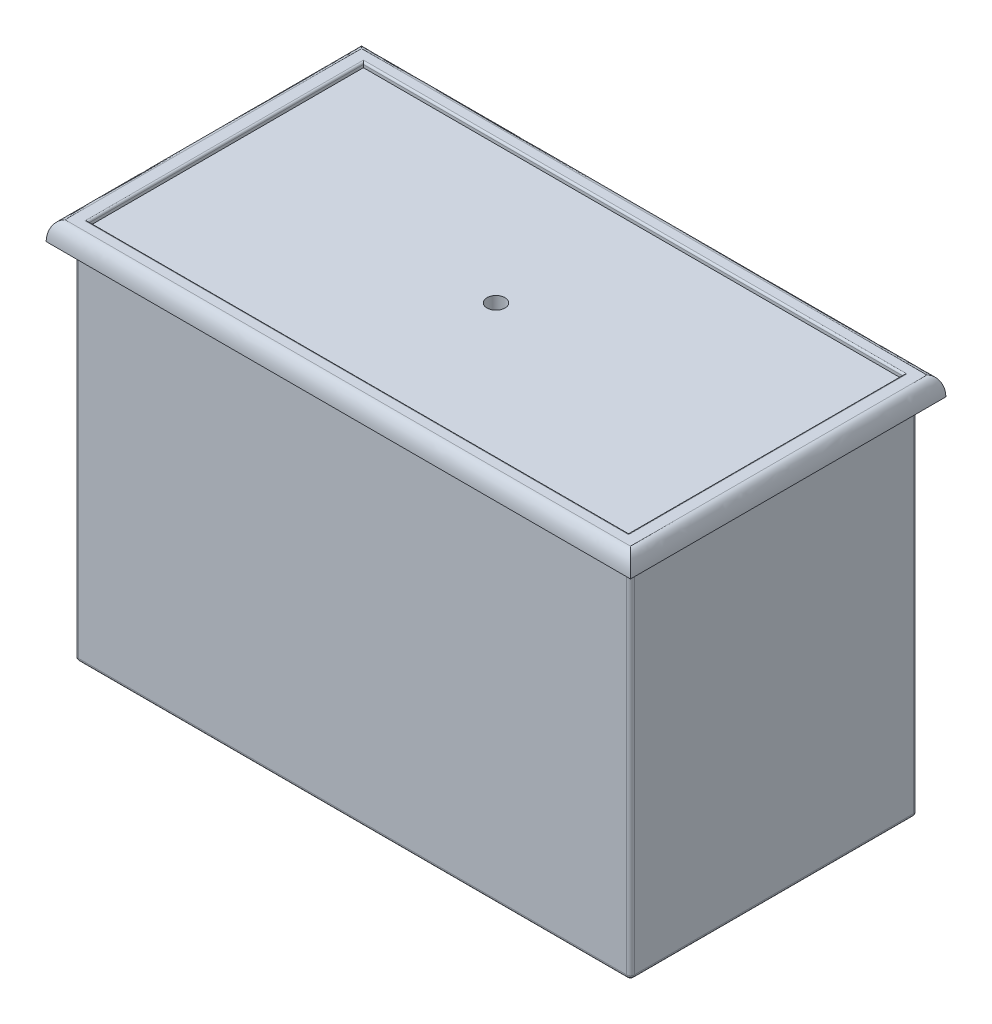
SolidWorks part; units mm, degrees
ref_plane "Front Plane" through (0, 0, 0) normal (0, 0, 1) x (1, 0, 0)
ref_plane "Top Plane" through (0, 0, 0) normal (0, 1, 0) x (1, 0, 0)
ref_plane "Right Plane" through (0, 0, 0) normal (1, 0, 0) x (0, 0, -1)
sketch "Sketch2" plane through (0, 0, 0) normal (0, 1, 0) x (1, 0, 0)
  line L0 (-290.5, 148.5) -> (290.5, 148.5)
  line L1 (-293.5, 151.5) -> (293.5, 151.5)
  line L2 (-293.5, 151.5) -> (-293.5, -151.5)
  line L3 (-293.5, -151.5) -> (293.5, -151.5)
  line L4 (293.5, 151.5) -> (293.5, -151.5)
  line L5 (-293.5, 151.5) -> (293.5, -151.5) construction
  line L6 (-293.5, -151.5) -> (293.5, 151.5) construction
  line L7 (290.5, 148.5) -> (290.5, -148.5)
  line L8 (-290.5, -148.5) -> (290.5, -148.5)
  line L9 (-290.5, 148.5) -> (-290.5, -148.5)
  point P0 (0, 0)
  dimension "D1" = 303
  dimension "D2" = 587
  dimension "D3" = 3
extrude "Walls" add sketch "Sketch2" along normal blind 380 contours L0 L7 L8 L9 | L2 L1 L4 L3
sketch "Sketch3" plane through (0, 0, 0) normal (0, -1, 0) x (1, 0, 0)
  line L1 (293.5, 151.5) -> (-293.5, 151.5)
  line L2 (293.5, 151.5) -> (293.5, -151.5)
  line L3 (293.5, -151.5) -> (-293.5, -151.5)
  line L4 (-293.5, 151.5) -> (-293.5, -151.5)
  line L5 (293.5, 151.5) -> (-293.5, -151.5) construction
  line L6 (293.5, -151.5) -> (-293.5, 151.5) construction
  point P0 (0, 0)
extrude "Base" add sketch "Sketch3" along normal blind 3
sketch "Sketch5" plane through (0, 380, 0) normal (0, 1, 0) x (1, 0, 0)
  line L8 (-308.5, -166.5) -> (308.5, -166.5)
  line L9 (-308.5, 166.5) -> (-308.5, -166.5)
  line L10 (308.5, -166.5) -> (308.5, 166.5)
  line L11 (308.5, 166.5) -> (-308.5, 166.5)
  line L12 (-308.5, -166.5) -> (308.5, -166.5)
  line L13 (-308.5, 166.5) -> (-308.5, -166.5)
  line L14 (308.5, -166.5) -> (308.5, 166.5)
  line L15 (308.5, 166.5) -> (-308.5, 166.5)
  dimension "D1" = 15
extrude "Lid" add sketch "Sketch5" along normal blind 20
sketch "Sketch7" plane through (0, 400, 0) normal (0, 1, 0) x (1, 0, 0)
  line L1 (-285, 145) -> (285, 145)
  line L2 (-285, 145) -> (-285, -145)
  line L3 (-285, -145) -> (285, -145)
  line L4 (285, 145) -> (285, -145)
  line L5 (-285, 145) -> (285, -145) construction
  line L6 (-285, -145) -> (285, 145) construction
  point P0 (0, 0)
  dimension "D1" = 570
  dimension "D2" = 290
extrude "Lid Divet" cut sketch "Sketch7" against normal blind 5
fillet "Fillet1" radius 20 4 edges at (0, 400, -166.5) (308.5, 400, 0) (0, 400, 166.5) (-308.5, 400, 0) second distance 10 first distance on face at (0, 390, -166.5) first distance on face at (308.5, 390, 0) first distance on face at (0, 390, 166.5) first distance on face at (-308.5, 390, 0)
fillet "Fillet2" radius 2 4 edges at (285, 400, 0) (0, 400, 145) (-285, 400, 0) (0, 400, -145)
fillet "Fillet3" radius 4 8 edges at (0, -3, 151.5) (293.5, -3, 0) (0, -3, -151.5) (-293.5, -3, 0) (293.5, 188.5, -151.5) (293.5, 188.5, 151.5) (-293.5, 188.5, -151.5) (-293.5, 188.5, 151.5)
sketch "Sketch8" plane through (0, 395, 0) normal (0, 1, 0) x (1, 0, 0)
  circle A0 centre (0, 0) radius 9.525
  dimension "D1" = 19.05
extrude "Inlet" cut sketch "Sketch8" against normal up to next
sketch "Sketch9" plane through (0, -3, 0) normal (0, -1, 0) x (1, 0, 0)
  line L0 (-289.5, 147.5) -> (-289.5, -147.5) construction
  circle A0 centre (-259.5, 0) radius 9.525
  dimension "D1" = 19.05
  dimension "D2" = 30
extrude "Cut-Extrude3" cut sketch "Sketch9" against normal up to next
equation "\"D1@Walls\" = 390 - 10"
